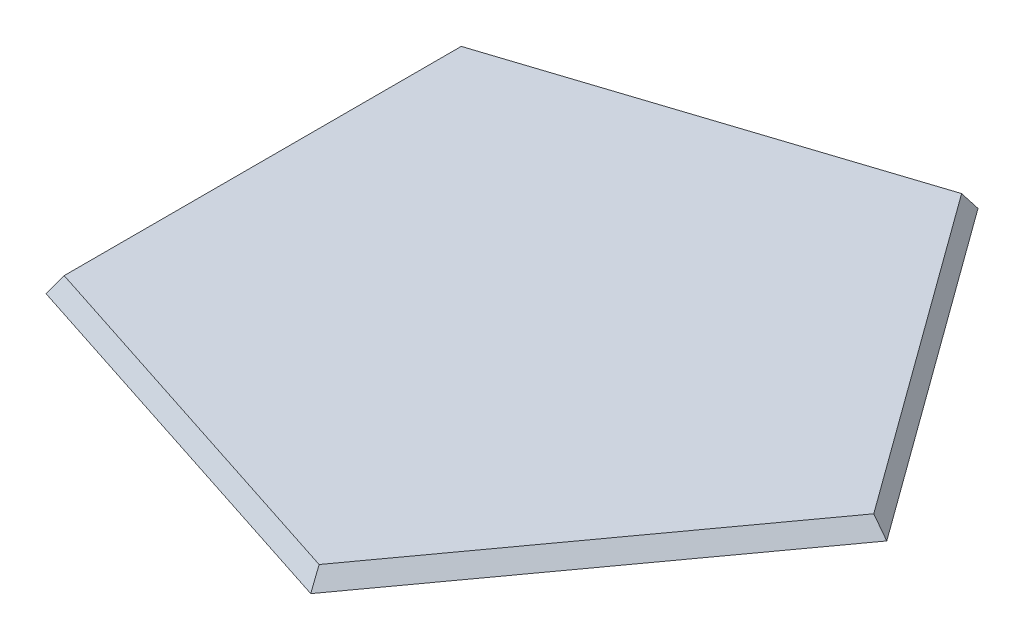
SolidWorks part; units mm, degrees
ref_plane "Front Plane" through (0, 0, 0) normal (0, 0, 1) x (1, 0, 0)
ref_plane "Top Plane" through (0, 0, 0) normal (0, 1, 0) x (1, 0, 0)
ref_plane "Right Plane" through (0, 0, 0) normal (1, 0, 0) x (0, 0, -1)
sketch "Sketch1" plane through (0, 0, 0) normal (0, 1, 0) x (1, 0, 0)
  line L1 (61.8034, 0) -> (19.0983, 58.7785)
  line L2 (19.0983, 58.7785) -> (-50, 36.3271)
  line L3 (-50, 36.3271) -> (-50, -36.3271)
  line L4 (-50, -36.3271) -> (19.0983, -58.7785)
  line L5 (19.0983, -58.7785) -> (61.8034, 0)
  circle A0 centre (0, 0) radius 50 construction
extrude "Boss-Extrude1" add sketch "Sketch1" along normal blind 3 contours L5 L1 L2 L3 L4
chamfer "Chamfer1" distance 3 angle 31.715 5 edges at (-50, 3, 0) (-15.4508, 3, -47.5528) (40.4508, 3, -29.3893) (40.4508, 3, 29.3893) (-15.4508, 3, 47.5528) first distance on face at (-50, 1.5, 0) first distance on face at (-15.4508, 1.5, -47.5528) first distance on face at (40.4508, 1.5, -29.3893) first distance on face at (40.4508, 1.5, 29.3893) first distance on face at (-15.4508, 1.5, 47.5528)
sketch3d "3DSketch1"
  line L0 (-44, 0, -31.9679) -> (-44, 0, 31.9679)
  line L1 (16.8065, 0, -51.7251) -> (-44, 0, -31.9679)
  line L2 (54.387, 0, 0) -> (16.8065, 0, -51.7251)
  line L3 (16.8065, 0, 51.7251) -> (54.387, 0, 0)
  line L4 (-44, 0, 31.9679) -> (16.8065, 0, 51.7251)
  line L5 (-44, 0, -31.9679) -> (-44, 0, 31.9679) construction
  line L6 (16.8065, 0, -51.7251) -> (-44, 0, -31.9679) construction
  line L7 (54.387, 0, 0) -> (16.8065, 0, -51.7251) construction
  line L8 (16.8065, 0, 51.7251) -> (54.387, 0, 0) construction
  line L9 (-44, 0, 31.9679) -> (16.8065, 0, 51.7251) construction
  dimension "D1" = 6
sketch "Sketch7" plane through (0, 0, 0) normal (0, -1, 0) x (1, 0, 0)
  circle A0 centre (16.8065, -51.7251) radius 2
sketch "Sketch9" plane through (0, 0, 0) normal (0, -1, 0) x (1, 0, 0)
  circle A0 centre (-44, -31.9679) radius 2
sketch "Sketch10" plane through (0, 0, 0) normal (0, -1, 0) x (1, 0, 0)
  circle A0 centre (54.387, 0) radius 2
sketch "Sketch11" plane through (0, 0, 0) normal (0, -1, 0) x (1, 0, 0)
  circle A0 centre (16.8065, 51.7251) radius 2
sketch "Sketch12" plane through (0, 0, 0) normal (0, -1, 0) x (1, 0, 0)
  circle A0 centre (-44, 31.9679) radius 2
extrude "Cut-Extrude6" cut sketch "Sketch7" along direction (-0.1876, 0.7947, 0.5773) on the side against the normal blind 1.5 contours A0
extrude "Cut-Extrude7" cut sketch "Sketch9" along direction (0.4911, 0.7947, 0.3568) on the side against the normal blind 1.5 contours A0
extrude "Cut-Extrude8" cut sketch "Sketch12" along direction (-0.4911, -0.7947, 0.3568) on the side against the normal blind 1.5 contours A0
extrude "Cut-Extrude9" cut sketch "Sketch11" along direction (-0.1876, 0.7947, -0.5773) on the side against the normal blind 1.5 contours A0
extrude "Cut-Extrude10" cut sketch "Sketch10" along direction (-0.607, 0.7947, 0) on the side against the normal blind 1.5 contours A0
sketch "Sketch13" plane through (0, 0, 0) normal (0, -1, 0) x (1, 0, 0)
  line L0 (-50, -36.3271) -> (40.4508, 29.3893) construction
  line L1 (19.0983, 58.7785) -> (61.8034, 0) construction
  line L2 (-50, 36.3271) -> (40.4508, -29.3893) construction
  line L3 (61.8034, 0) -> (19.0983, -58.7785) construction
  line L4 (19.0983, 58.7785) -> (-15.4508, -47.5528) construction
  line L5 (19.0983, -58.7785) -> (-50, -36.3271) construction
  line L6 (61.8034, 0) -> (-50, 0) construction
  line L7 (-50, -36.3271) -> (-50, 36.3271) construction
  line L8 (19.0983, -58.7785) -> (-15.4508, 47.5528) construction
  line L9 (-50, 36.3271) -> (19.0983, 58.7785) construction
